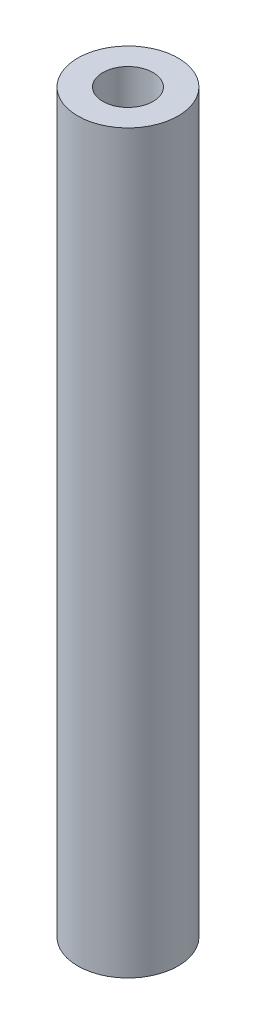
SolidWorks part; units mm, degrees
ref_plane "Front Plane" through (0, 0, 0) normal (0, 0, 1) x (1, 0, 0)
ref_plane "Top Plane" through (0, 0, 0) normal (0, 1, 0) x (1, 0, 0)
ref_plane "Right Plane" through (0, 0, 0) normal (1, 0, 0) x (0, 0, -1)
sketch "Sketch1" plane through (0, 0, 0) normal (0, 1, 0) x (1, 0, 0)
  circle A0 centre (0, 0) radius 1.5
  circle A1 centre (0, 0) radius 3
  dimension "D1" = 3
  dimension "D2" = 6
extrude "Boss-Extrude1" add sketch "Sketch1" along normal blind 44
